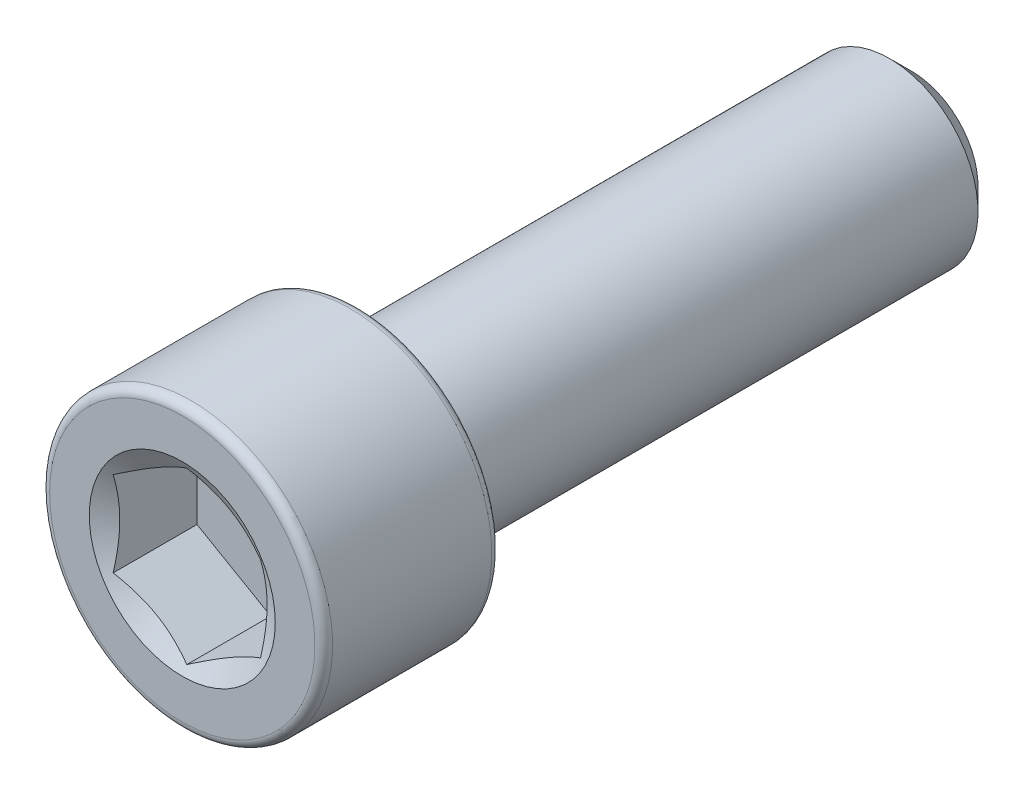
SolidWorks part; units mm, degrees
material "Alloy Steel (SS)"
ref_plane "Front Plane" through (0, 0, 0) normal (0, 0, 1) x (1, 0, 0)
ref_plane "Top Plane" through (0, 0, 0) normal (0, 1, 0) x (1, 0, 0)
ref_plane "Right Plane" through (0, 0, 0) normal (1, 0, 0) x (0, 0, -1)
sketch "Sketch1" plane through (0, 0, 0) normal (1, 0, 0) x (0, 0, -1)
  line L0 (3.1433, 0) -> (-3.1433, 0) construction
  line L1 (-1.6193, 1.2192) -> (-1.6193, -1.2192) construction
  line L2 (3.1433, 0.762) -> (3.1433, -0.762) construction
  line L3 (3.1234, 0.7964) -> (3.2822, 0.5214) construction
  line L4 (3.2623, 0.5558) -> (3.302, 0.5558) construction
  line L5 (3.2822, 0.5214) -> (3.4409, 0.7964) construction
  line L6 (3.4409, 0.7964) -> (3.1234, 0.7964) construction
  line L7 (3.2822, 0.5558) -> (3.2822, 0.5214) construction
  line L8 (3.2822, 0.7964) -> (3.2822, 0.762) construction
  line L9 (3.4211, 0.762) -> (3.1433, 0.762) construction
  point P4 (-1.6193, 0)
  point P6 (-1.6192, 0.635)
  point P7 (2.3495, -0.762)
  point P20 (3.2822, 0.7792)
  dimension "Head Height" = 1.524
  dimension "Head Diameter" = 2.4384
  dimension "Drive Size" = 1.27
  dimension "Length" = 4.7625
  dimension "Screw Size Decimal Equivalent" = 1.524
  dimension "Pitch" = 0.3175
  dimension "Pitch/8" = 0.0397
  dimension "Thread Note" = 0.7937
sketch "Sketch2" plane through (0, 0, 0) normal (1, 0, 0) x (0, 0, -1)
  line L0 (3.1433, 0) -> (3.1433, 0.5715)
  line L1 (3.1433, 0.762) -> (3.1433, -0.762) construction
  line L2 (3.1433, 0.5715) -> (2.9528, 0.762)
  line L3 (2.9528, 0.762) -> (-1.6193, 0.762)
  line L4 (-1.6193, 0.762) -> (-1.6193, 1.143)
  line L5 (-1.6955, 1.2192) -> (-3.0671, 1.2192)
  line L6 (-3.1433, 1.143) -> (-3.1433, 0)
  line L7 (3.1433, 0) -> (-3.1433, 0) construction
  line L8 (-3.1433, 0) -> (3.1433, 0)
  arc A0 (-1.6193, 1.143) -> (-1.6955, 1.2192) centre (-1.6955, 1.143) ccw
  arc A1 (-3.0671, 1.2192) -> (-3.1433, 1.143) centre (-3.0671, 1.143) ccw
  point P19 (-1.6193, 1.2192)
  dimension "D3" = 0.0762
  dimension "D1" = 0.1905
  dimension "D2" = 45
revolve "Revolve1" add sketch "Sketch2" angle 360 about L0
sketch "Sketch3" plane through (0, 0, 0) normal (0, 0, 1) x (1, 0, 0)
  line L1 (-0.635, 0.3666) -> (-0.635, -0.3666)
  line L2 (-0.635, -0.3666) -> (0, -0.7332)
  line L3 (0, -0.7332) -> (0.635, -0.3666)
  line L4 (0.635, -0.3666) -> (0.635, 0.3666)
  line L5 (0.635, 0.3666) -> (0, 0.7332)
  line L6 (0, 0.7332) -> (-0.635, 0.3666)
  circle A0 centre (0, 0) radius 0.635 construction
  circle A1 centre (0, 0) radius 1.2192 construction
extrude "Cut-Extrude1" cut sketch "Sketch3" against normal blind 0.762 from vertex starting at point (0, 0, 3.1433)
sketch "Sketch4" plane through (0, 0, 3.1433) normal (0, 0, 1) x (1, 0, 0)
  line L0 (0, 0.7332) -> (0, 0.8698) construction
  line L1 (0, 0.8698) -> (0, 1.0064) construction
  line L2 (0, 1.0064) -> (0, 1.143) construction
  circle A0 centre (0, 0) radius 0.8015
  point P12 (0, 0.8015)
extrude "Cut-Extrude2" cut sketch "Sketch4" against normal through all draft 60
split "Split1" [suppressed] bodies to split 106 112
sketch "Sketch5" [suppressed] plane through (0, 0, 0) normal (1, 0, 0) x (0, 0, -1)
  line L0 (3.2623, 0.5558) -> (3.302, 0.5558)
  line L1 (3.302, 0.5558) -> (3.431, 0.7792)
  line L2 (3.431, 0.7792) -> (3.1333, 0.7792)
  line L3 (3.1333, 0.7792) -> (3.2623, 0.5558)
  line L4 (3.1234, 0.7964) -> (3.2822, 0.5214) construction
sketch "Sketch6" [suppressed] plane through (0, 0, -3.1433) normal (0, 0, -1) x (-1, 0, 0)
  circle A0 centre (0, 0) radius 0.762
curve "Helix/Spiral1" [suppressed] pitch 0.3175 height 5.08 turns 16
sweep "Cut-Sweep1" [suppressed] cut profiles "Sketch5" path "Helix/Spiral1"
sketch "Sketch7" [suppressed] plane through (0, 0, 1.6193) normal (0, 0, -1) x (-1, 0, 0)
  circle A0 centre (0, 0) radius 0.8128
  circle A1 centre (0, 0) radius 0.762 construction
  dimension "D1" = 0.0508
extrude "Boss-Extrude1" [suppressed] add sketch "Sketch7" along normal blind 0.9525 draft 20 and the other way blind 0.1524
ref_plane "Plane1" [suppressed] through (0, 0, 2.1222) normal (0, 0, -1) x (-1, 0, 0)
sketch "Sketch13" [suppressed] plane through (0, 0, 2.1222) normal (0, 0, -1) x (-1, 0, 0)
  line L0 (0.0305, 1.2188) -> (0, 0) construction
  line L1 (0, 0) -> (-0.0305, 1.2188) construction
  line L3 (0.03, 1.1987) -> (0.0305, 1.2188)
  line L6 (-0.03, 1.1987) -> (-0.0305, 1.2188)
  arc A1 (0.0305, 1.2188) -> (-0.0305, 1.2188) centre (0, 0) ccw
  circle A2 centre (0, 0) radius 1.2192 construction
  arc A3 (0.03, 1.1987) -> (-0.03, 1.1987) centre (0, 0) ccw
  point P2 (0, 1.2192)
  dimension "D3" = 0.0201
  dimension "D1" = 0.061
extrude "Cut-Extrude3" [suppressed] cut sketch "Sketch13" against normal blind 0.8504
chamfer "Chamfer3" [suppressed] distance 0.0201 angle 60
chamfer "Chamfer4" [suppressed] distance 0.0201 angle 85
pattern_circular "CirPattern2" [suppressed] count 50 over 360 about axis through (0, 0, -3.1433) along (0, 0, 1) of bodies 134
equation "\"Pitch/8@Sketch1\" = \"Pitch@Sketch1\" / 8"
equation "\"Thread Note@Sketch1\"=\"Pitch@Sketch1\" * 2.5"
equation "\"D1@Sketch2\"=\"Pitch@Sketch1\"*.60"
equation "\"D3@Sketch2\"=\"Head Height@Sketch1\"*.05"
equation "\"D1@Cut-Extrude1\" = \"Head Height@Sketch1\" * .5"
equation "\"D3@Helix/Spiral1\" = \"Length@Sketch1\" + \"Pitch@Sketch1\""
equation "\"D4@Helix/Spiral1\" = \"Pitch@Sketch1\""
equation "\"D2@Boss-Extrude1\" = \"Head Height@Sketch1\" * .1"
equation "\"D1\"= \"Screw Size Decimal Equivalent@Sketch1\" * .4"
equation "\"D1@Plane1\"=\"Head Height@Sketch1\" * .33"
equation "\"D1@Cut-Extrude3\"=( \"Head Height@Sketch1\" - \"D1@Plane1\" - \"D3@Sketch2\" )  * .9"
equation "\"D1@Chamfer3\"=\"D3@Sketch13\""
equation "\"D1@Chamfer4\"=\"D3@Sketch13\""
equation "\"D1@CirPattern2\"=( \"Head Diameter@Sketch1\" * pi )  /  ( 2.5*\"D1@Sketch13\" )"
equation "\"D1@Sketch13\"=\"Head Diameter@Sketch1\" * .025"
equation "\"D3@Sketch13\"=\"D1@Sketch13\"*.33"
equation "\"D1@Boss-Extrude1\"=\"Pitch@Sketch1\"*3"
